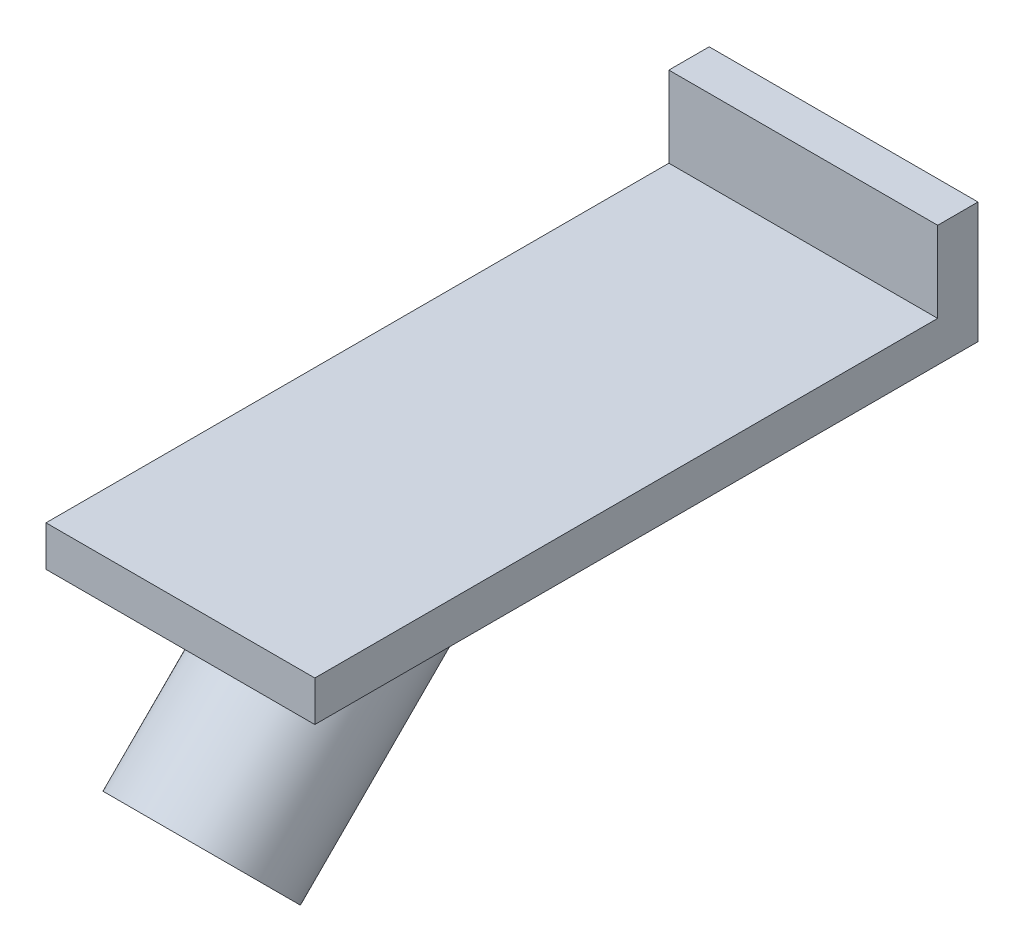
SolidWorks part; units mm, degrees
ref_plane "Front Plane" through (0, 0, 0) normal (0, 0, 1) x (1, 0, 0)
ref_plane "Top Plane" through (0, 0, 0) normal (0, 1, 0) x (1, 0, 0)
ref_plane "Right Plane" through (0, 0, 0) normal (1, 0, 0) x (0, 0, -1)
ref_plane "Plane1" through (83.8446, 0, 0) normal (1, 0, 0) x (0, 0, -1)
sketch "Sketch1" plane through (83.8446, 0, 0) normal (1, 0, 0) x (0, 0, -1)
  line L0 (-93.9922, 62.6349) -> (-93.9922, 118.6349) construction
  line L1 (-149.9922, 62.6349) -> (-93.9922, 62.6349) construction
  line L2 (-93.9922, 62.6349) -> (-93.9922, 68.6349)
  line L3 (-118.9922, 62.6349) -> (-93.9922, 62.6349)
  line L4 (-118.9922, 59.6349) -> (-90.9922, 59.6349)
  line L5 (-90.9922, 59.6349) -> (-90.9922, 68.6349)
  line L6 (-93.9922, 68.6349) -> (-90.9922, 68.6349)
  line L8 (-149.9922, 59.6349) -> (-90.9922, 59.6349) construction
  line L9 (-149.9922, 62.6349) -> (-93.9922, 62.6349) construction
  line L10 (-90.9922, 59.6349) -> (-90.9922, 118.6349) construction
  line L11 (-93.9922, 62.6349) -> (-93.9922, 118.6349) construction
  line L12 (-118.9922, 62.6349) -> (-140.3338, 62.6349)
  line L13 (-140.3338, 62.6349) -> (-140.3338, 59.6349)
  line L14 (-140.3338, 59.6349) -> (-118.9922, 59.6349)
  dimension "D2" = 6
  dimension "D1" = 3
extrude "Boss-Extrude1" add sketch "Sketch1" against normal blind 20
ref_plane "Plane2" through (0, -46.4378, 46.4378) normal (0, 0.7071, -0.7071) x (1, 0, 0)
sketch "Sketch2" plane through (0, -46.4378, 46.4378) normal (0, 0.7071, -0.7071) x (1, 0, 0)
  circle A0 centre (73.8446, -130.5511) radius 3
  arc A4 (72.1863, -128.0511) -> (75.5029, -128.0511) centre (73.8446, -130.5511) ccw construction
  circle A5 centre (73.8446, -130.5511) radius 6
  dimension "D2" = 6
  dimension "D1" = 3
extrude "Boss-Extrude2" add sketch "Sketch2" along normal up to next
fillet "Fillet1" radius 2 1 edges at (73.8446, 59.6349, 133.4775)
ref_plane "Plane3" through (0, -44.67, 44.67) normal (0, -0.7071, 0.7071) x (-1, 0, 0)
sketch "Sketch3" plane through (0, -44.67, 44.67) normal (0, -0.7071, 0.7071) x (-1, 0, 0)
  circle A0 centre (-73.8446, -130.5511) radius 3 construction
  circle A1 centre (-73.8446, -130.5511) radius 3
extrude "Boss-Extrude3" add sketch "Sketch3" against normal up to surface (19.9584 mm away)
